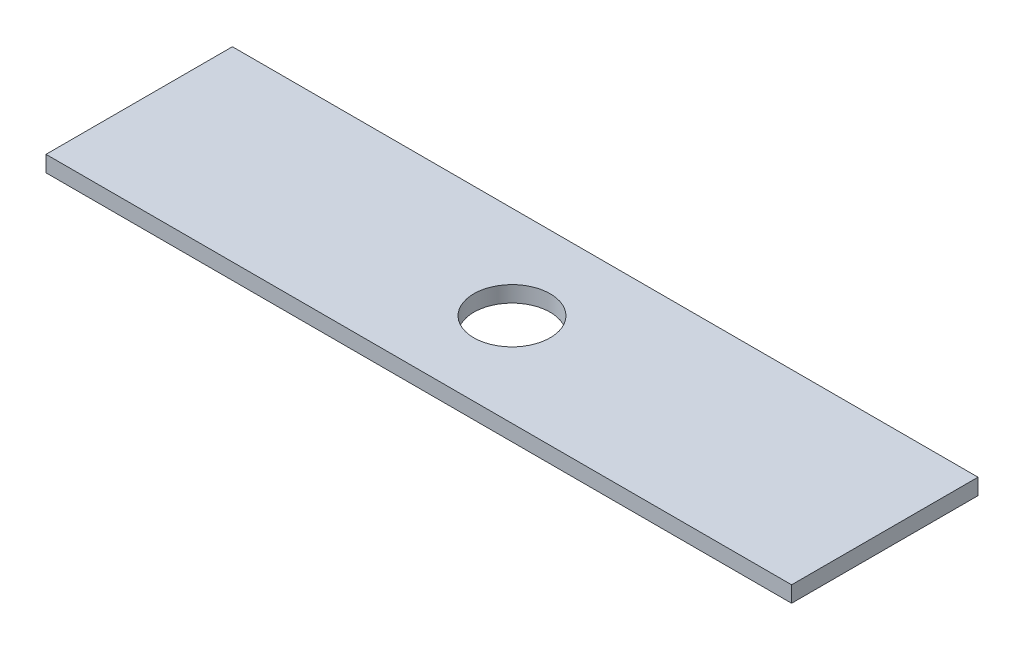
SolidWorks part; units mm, degrees
ref_plane "Front Plane" through (0, 0, 0) normal (0, 0, 1) x (1, 0, 0)
ref_plane "Top Plane" through (0, 0, 0) normal (0, 1, 0) x (1, 0, 0)
ref_plane "Right Plane" through (0, 0, 0) normal (1, 0, 0) x (0, 0, -1)
sketch "Sketch1" plane through (0, 0, 0) normal (0, 1, 0) x (1, 0, 0)
  line L1 (-50, 12.5) -> (50, 12.5)
  line L2 (-50, 12.5) -> (-50, -12.5)
  line L3 (-50, -12.5) -> (50, -12.5)
  line L4 (50, 12.5) -> (50, -12.5)
  line L5 (-50, 12.5) -> (50, -12.5) construction
  line L6 (-50, -12.5) -> (50, 12.5) construction
  point P0 (0, 0)
  dimension "D1" = 25
  dimension "D2" = 100
extrude "Boss-Extrude1" add sketch "Sketch1" along normal blind 1.075 and the other way blind 1.075
sketch "Sketch2" plane through (0, 0, 0) normal (0, 1, 0) x (1, 0, 0)
  circle A0 centre (0, 0) radius 5.12
  dimension "D1" = 10.24
extrude "Cut-Extrude1" cut sketch "Sketch2" against normal through all and the other way through all
